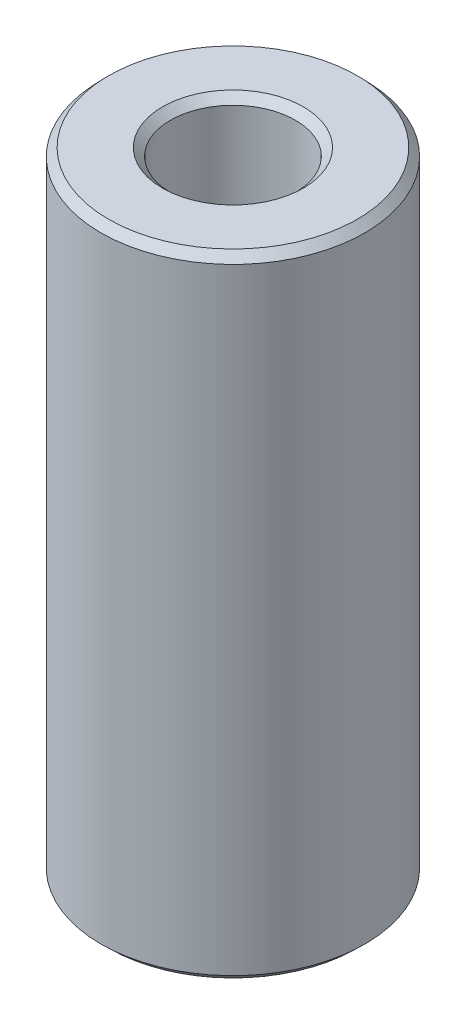
SolidWorks part; units mm, degrees
ref_plane "Front Plane" through (0, 0, 0) normal (0, 0, 1) x (1, 0, 0)
ref_plane "Top Plane" through (0, 0, 0) normal (0, 1, 0) x (1, 0, 0)
ref_plane "Right Plane" through (0, 0, 0) normal (1, 0, 0) x (0, 0, -1)
sketch "Sketch1" plane through (0, 0, 0) normal (0, 1, 0) x (1, 0, 0)
  circle A0 centre (0, 0) radius 47.5
  dimension "SLEEVE_OD" = 95
extrude "Boss-Extrude1" add sketch "Sketch1" along normal blind 227.2458
sketch "Sketch2" plane through (0, 0, 0) normal (0, 1, 0) x (1, 0, 0)
  circle A0 centre (0, 0) radius 22.4992
  dimension "BORE_D" = 44.9984
extrude "Cut-Extrude1" cut sketch "Sketch2" along normal through all
chamfer "Chamfer1" distance 2.858 angle 43.891 4 edges at (0, 227.2458, 22.4992) (0, 0, 22.4992) (0, 0, 47.5) (0, 227.2458, 47.5) first distance on face at (0, 227.2458, 22.4992) first distance on face at (0, 0, 22.4992) first distance on face at (0, 227.2458, 47.5)
